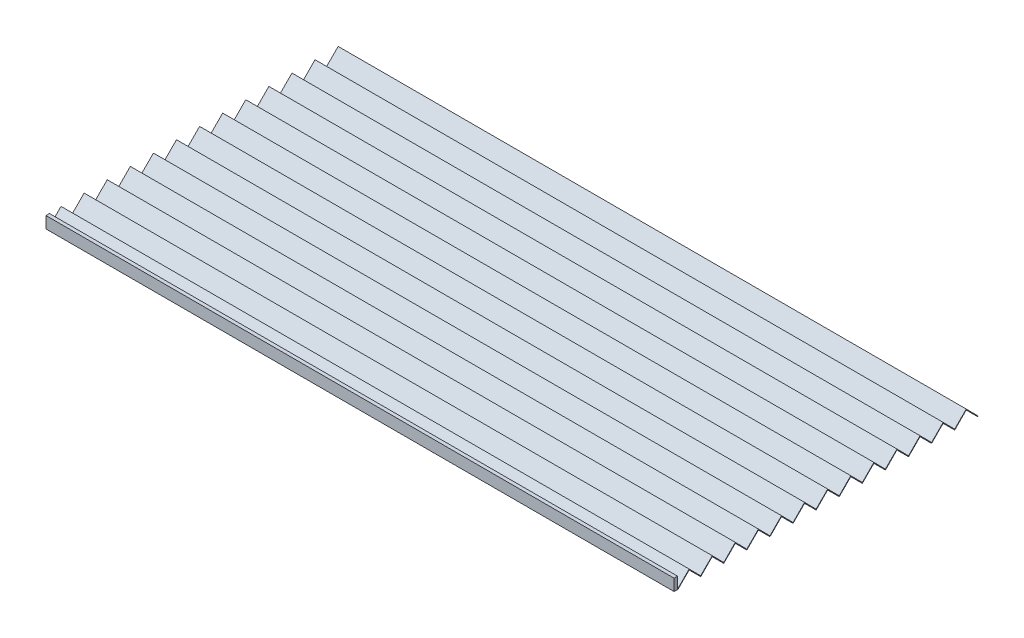
SolidWorks part; units mm, degrees
ref_plane "Front Plane" through (0, 0, 0) normal (0, 0, 1) x (1, 0, 0)
ref_plane "Top Plane" through (0, 0, 0) normal (0, 1, 0) x (1, 0, 0)
ref_plane "Right Plane" through (0, 0, 0) normal (1, 0, 0) x (0, 0, -1)
sketch "Sketch2" plane through (0, 0, 0) normal (0, 0, 1) x (1, 0, 0)
  line L1 (-270, 10) -> (270, 10)
  line L2 (-270, 10) -> (-270, 0)
  line L3 (-270, 0) -> (270, 0)
  line L4 (270, 10) -> (270, 0)
  point P4 (0, 0)
  dimension "D1" = 10
  dimension "D2" = 540
extrude "Boss-Extrude1" add sketch "Sketch2" along normal blind 3
sketch "Sketch3" plane through (270, 0, 0) normal (1, 0, 0) x (0, 0, -1)
  line L0 (0, 10) -> (258.0832, 10) construction
  line L1 (0, 0) -> (258.0832, 0) construction
  line L3 (0, 0) -> (9.9263, 10)
  line L4 (9.9263, 10) -> (19.8526, 0)
  line L5 (19.8526, 0) -> (29.7788, 10)
  line L6 (29.7788, 10) -> (39.7051, 0)
  line L7 (39.7051, 0) -> (49.6314, 10)
  line L8 (49.6314, 10) -> (59.5577, 0)
  line L9 (59.5577, 0) -> (69.484, 10)
  line L10 (69.484, 10) -> (79.4102, 0)
  line L11 (79.4102, 0) -> (89.3365, 10)
  line L12 (89.3365, 10) -> (99.2628, 0)
  line L13 (99.2628, 0) -> (109.1891, 10)
  line L14 (109.1891, 10) -> (119.1153, 0)
  line L15 (119.1153, 0) -> (129.0416, 10)
  line L16 (129.0416, 10) -> (138.9679, 0)
  line L17 (138.9679, 0) -> (148.8942, 10)
  line L18 (148.8942, 10) -> (158.8205, 0)
  line L20 (158.8205, 0) -> (168.7467, 10)
  line L21 (168.7467, 10) -> (178.673, 0)
  line L22 (178.673, 0) -> (188.5993, 10)
  line L23 (188.5993, 10) -> (198.5256, 0)
  line L24 (198.5256, 0) -> (208.4519, 10)
  line L25 (208.4519, 10) -> (218.3781, 0)
  line L26 (218.3781, 0) -> (228.3044, 10)
  line L27 (228.3044, 10) -> (238.2307, 0)
  line L28 (238.2307, 0) -> (248.157, 10)
  line L29 (248.157, 10) -> (258.0832, 0)
  line L30 (258.0832, 10) -> (258.0832, 0) construction
  line L32 (258.0832, 10) -> (258.0832, 0) construction
extrude "Extrude-Thin1" add sketch "Sketch3" against normal through all thin thin type mid plane wall 0.5
